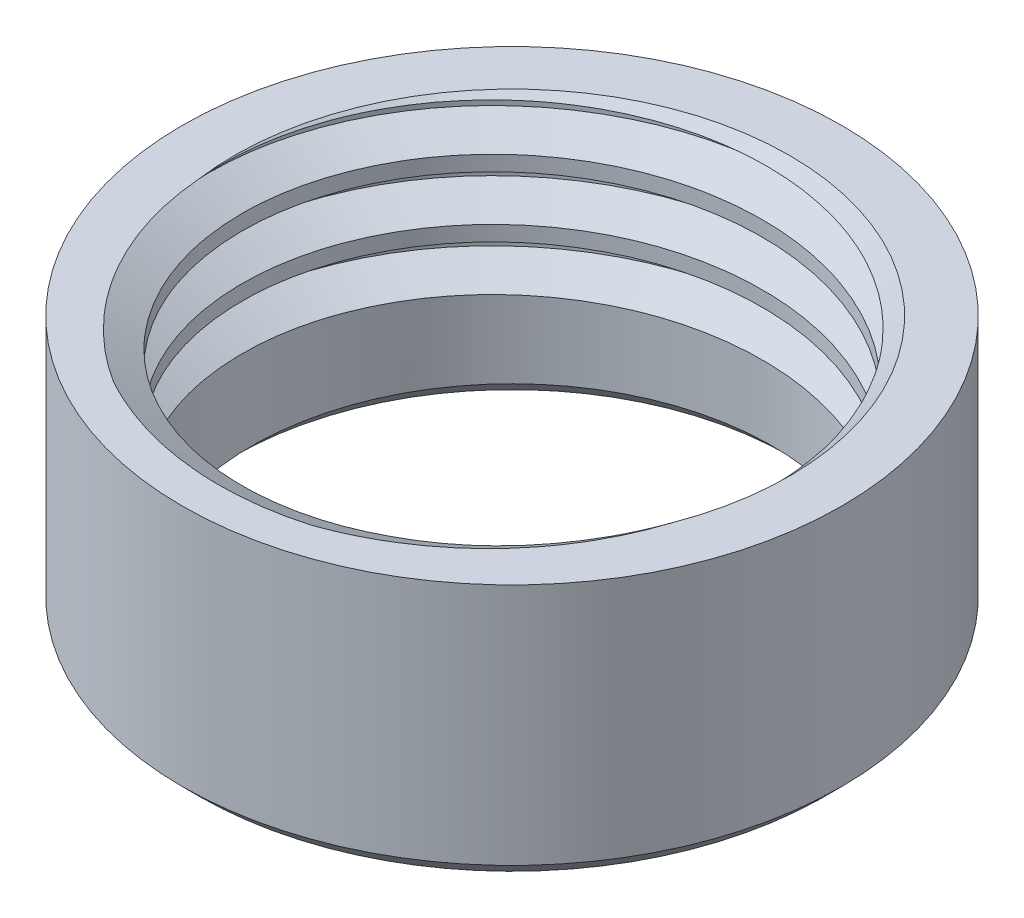
SolidWorks part; units mm, degrees
ref_plane "Front Plane" through (0, 0, 0) normal (0, 0, 1) x (1, 0, 0)
ref_plane "Top Plane" through (0, 0, 0) normal (0, 1, 0) x (1, 0, 0)
ref_plane "Right Plane" through (0, 0, 0) normal (1, 0, 0) x (0, 0, -1)
sketch "Sketch1" plane through (0, 0, 0) normal (0, 1, 0) x (1, 0, 0)
  circle A0 centre (0, 0) radius 15
  circle A1 centre (0, 0) radius 19
  dimension "D1" = 30
  dimension "D2" = 4
extrude "Boss-Extrude1" add sketch "Sketch1" along normal blind 15
chamfer "Chamfer1" distance 1 angle 45 1 edges at (0, 15, 15)
thread "Thread2" pitch 3.5 method cut profile "Thread Profile2" start angle 0, offset 5, length 12, pitch 3.5, diameter 30
ref_plane "Plane2" through (-15, 19, 0) normal (0, 0, 1) x (-1, 0, 0)
sketch "Thread Profile2" plane through (-15, 19, 0) normal (0, 0, 1) x (-1, 0, 0)
  line L0 (0, 0) -> (0, 3.5) construction
  line L1 (0, 0) -> (1.8944, 1.0937)
  line L2 (1.8944, 1.0937) -> (1.8944, 1.5312)
  line L3 (1.8944, 1.5312) -> (0, 2.625)
  line L4 (1.8944, 1.3125) -> (0, 1.3125) construction
  line L11 (0, 0) -> (0, 2.625)
  point P2 (0, 0)
  dimension "Pitch" = 3.5
  dimension "Profile_Angle" = 60
  dimension "Profile_Land" = 0.4375
  dimension "Profile_Height" = 1.8944
chamfer "Chamfer2" distance 1 angle 45 2 edges at (0, 0, 15) (0, 0, 19)
